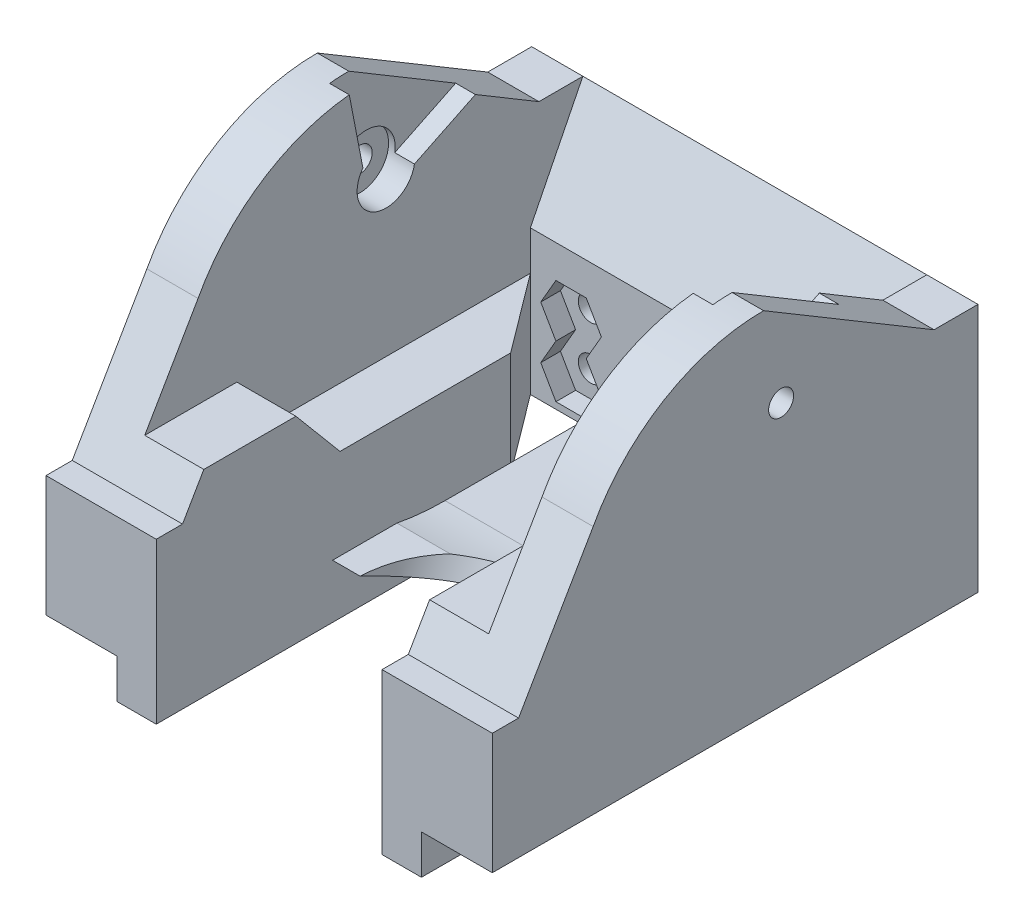
SolidWorks part; units mm, degrees
ref_plane "Alzado" through (0, 0, 0) normal (0, 0, 1) x (1, 0, 0)
ref_plane "Planta" through (0, 0, 0) normal (0, 1, 0) x (1, 0, 0)
ref_plane "Vista lateral" through (0, 0, 0) normal (1, 0, 0) x (0, 0, -1)
sketch "Croquis1" plane through (0, 0, 0) normal (0, 0, 1) x (1, 0, 0)
  line L1 (-48.8873, 14.6225) -> (-14.8873, 14.6225)
  line L2 (-48.8873, 14.6225) -> (-48.8873, -4.3775)
  line L3 (-48.8873, -4.3775) -> (-14.8873, -4.3775)
  line L4 (-14.8873, 14.6225) -> (-14.8873, -4.3775)
  dimension "D1" = 19
  dimension "D2" = 34
extrude "Saliente-Extruir1" add sketch "Croquis1" along normal blind 35
sketch "Croquis2" plane through (0, -4.3775, 0) normal (0, -1, 0) x (1, 0, 0)
  line L0 (-48.8873, 35) -> (-14.8873, 35) construction
  line L1 (-44.9873, 35) -> (-18.7873, 35)
  line L2 (-44.9873, 35) -> (-44.9873, 4)
  line L3 (-44.9873, 4) -> (-18.7873, 4)
  line L4 (-18.7873, 35) -> (-18.7873, 4)
  line L5 (-48.8873, 35) -> (-48.8873, 0) construction
  line L6 (-14.8873, 35) -> (-14.8873, 0) construction
  line L7 (-48.8873, 0) -> (-14.8873, 0) construction
  dimension "D1" = 3.9
  dimension "D2" = 3.9
  dimension "D3" = 26.2
  dimension "D4" = 4
extrude "Cortar-Extruir1" cut sketch "Croquis2" against normal blind 25
sketch "Croquis4" plane through (-18.7873, 0, 0) normal (-1, 0, 0) x (0, 0, 1)
  line L0 (4, 14.6225) -> (4, 6.6225)
  line L1 (4, 14.6225) -> (4, -4.3775) construction
  line L2 (4, 6.6225) -> (0, 14.6225)
  line L3 (0, 14.6225) -> (4, 14.6225)
extrude "Cortar-Extruir3" cut sketch "Croquis4" along normal up to vertex (26.2 mm away) up to point (-44.9873, 14.6225, 4)
sketch "Croquis9" plane through (-14.8873, 0, 0) normal (1, 0, 0) x (0, 0, -1)
  line L0 (-35, 14.6225) -> (0, 14.6225) construction
  line L1 (-29.3158, 14.6225) -> (-3.3495, 14.6225)
  line L7 (-35, -4.3775) -> (0, -4.3775) construction
  arc A0 (-29.3158, 14.6225) -> (-3.3495, 14.6225) centre (-16.3327, 7.6225) cw
  dimension "D2" = 12
extrude "Saliente-Extruir2" add sketch "Croquis9" against normal up to vertex (34 mm away) up to point (-48.8873, 14.6225, 35)
sketch "Croquis10" plane through (0, 14.6225, 0) normal (0, -1, 0) x (1, 0, 0)
  line L1 (-44.9873, 29.3158) -> (-18.7873, 29.3158)
  line L2 (-44.9873, 29.3158) -> (-44.9873, 3.3495)
  line L3 (-44.9873, 3.3495) -> (-18.7873, 3.3495)
  line L4 (-18.7873, 29.3158) -> (-18.7873, 3.3495)
extrude "Cortar-Extruir4" cut sketch "Croquis10" against normal blind 10
sketch "Croquis18" plane through (0, 0, 0) normal (0, 0, -1) x (-1, 0, 0)
  line L0 (48.8873, -4.3775) -> (14.8873, -4.3775) construction
  line L2 (48.8873, 14.6225) -> (48.8873, -4.3775) construction
  circle A0 centre (41.8873, -1.8775) radius 0.95
  circle A1 centre (21.8873, -1.8775) radius 0.95
  circle A2 centre (21.8873, 2.1225) radius 0.95
  circle A3 centre (41.8873, 2.1225) radius 0.95
  dimension "D1" = 2.5
  dimension "D2" = 7
  dimension "D5" = 4
  dimension "D3" = 2
  dimension "D4" = 2
extrude "Cortar-Extruir11" cut sketch "Croquis18" against normal up to vertex (4 mm away) up to point (-18.7873, -4.3775, 4)
sketch "Croquis19" plane through (0, 0, 4) normal (0, 0, 1) x (1, 0, 0)
  line L0 (-44.1973, -1.8775) -> (-43.0423, -3.878)
  line L1 (-24.1973, -1.8775) -> (-23.0423, -3.878)
  line L2 (-23.0423, -3.878) -> (-20.7323, -3.878)
  line L3 (-20.7323, -3.878) -> (-19.5773, -1.8775)
  line L4 (-19.5773, -1.8775) -> (-20.732, 0.1225)
  line L6 (-23.0426, 0.1225) -> (-24.1973, -1.8775)
  line L7 (-43.0423, -3.878) -> (-40.7323, -3.878)
  line L8 (-40.7323, -3.878) -> (-39.5773, -1.8775)
  line L9 (-39.5773, -1.8775) -> (-40.732, 0.1225)
  line L11 (-43.0426, 0.1225) -> (-44.1973, -1.8775)
  line L12 (-44.1973, 2.1225) -> (-43.0426, 0.1225)
  line L14 (-40.732, 0.1225) -> (-39.5773, 2.1225)
  line L15 (-39.5773, 2.1225) -> (-40.7323, 4.1231)
  line L16 (-40.7323, 4.1231) -> (-43.0423, 4.1231)
  line L17 (-43.0423, 4.1231) -> (-44.1973, 2.1225)
  line L18 (-24.1973, 2.1225) -> (-23.0426, 0.1225)
  line L20 (-20.732, 0.1225) -> (-19.5773, 2.1225)
  line L21 (-19.5773, 2.1225) -> (-20.7323, 4.1231)
  line L22 (-20.7323, 4.1231) -> (-23.0423, 4.1231)
  line L23 (-23.0423, 4.1231) -> (-24.1973, 2.1225)
  line L45 (-20.7323, 0.1231) -> (-23.0423, 0.1231) [skipped]
  line L46 (-23.0423, 0.122) -> (-20.7323, 0.122) [skipped]
  line L47 (-43.0423, 0.122) -> (-40.7323, 0.122) [skipped]
  circle A0 centre (-41.8873, -1.8775) radius 2.0005 construction
  circle A1 centre (-21.8873, -1.8775) radius 2.0005 construction
  circle A2 centre (-41.8873, 2.1225) radius 2.0005 construction
  circle A3 centre (-21.8873, 2.1225) radius 2.0005 construction
  dimension "D2" = 2
  dimension "D3" = 2
extrude "Cortar-Extruir12" cut sketch "Croquis19" against normal blind 1.5
sketch "Croquis21" plane through (-14.8873, 0, 0) normal (1, 0, 0) x (0, 0, -1)
  line L0 (0, -4.3775) -> (0, 14.6225) construction
  line L2 (-35, -4.3775) -> (0, -4.3775) construction
  circle A0 centre (-15, 15.6225) radius 0.95
  dimension "D1" = 15
  dimension "D2" = 20
extrude "Cortar-Extruir14" cut sketch "Croquis21" against normal up to vertex (34 mm away) up to point (-48.8873, 14.6225, 3.3495)
sketch "Croquis23" plane through (0, -4.3775, 0) normal (0, -1, 0) x (1, 0, 0)
  line L0 (-44.9873, 35) -> (-40.4873, 35)
  line L1 (-40.4873, 35) -> (-40.4873, 10)
  line L2 (-40.4873, 10) -> (-44.9873, 4)
  line L3 (-44.9873, 35) -> (-44.9873, 4) construction
  line L4 (-44.9873, 4) -> (-44.9873, 35)
  line L5 (-18.7873, 35) -> (-23.2873, 35)
  line L6 (-23.2873, 35) -> (-23.2873, 10)
  line L7 (-23.2873, 10) -> (-18.7873, 4)
  line L8 (-18.7873, 4) -> (-18.7873, 35)
  dimension "D1" = 25
  dimension "D2" = 25
extrude "Saliente-Extruir3" add sketch "Croquis23" against normal blind 8
sketch "Croquis25" plane through (0, -4.3775, 0) normal (0, -1, 0) x (1, 0, 0)
  line L0 (-40.4873, 35) -> (-43.4873, 35)
  line L1 (-20.2873, 35) -> (-23.2873, 35)
  line L2 (-43.4873, 35) -> (-43.4873, 10)
  line L3 (-43.4873, 10) -> (-40.4873, 10)
  line L4 (-40.4873, 35) -> (-40.4873, 10)
  line L10 (-20.2873, 35) -> (-20.2873, 10)
  line L11 (-20.2873, 10) -> (-23.2873, 10)
  line L12 (-23.2873, 35) -> (-23.2873, 10)
  dimension "D1" = 3
  dimension "D2" = 3
extrude "Saliente-Extruir4" add sketch "Croquis25" along normal blind 3
sketch "Croquis43" plane through (0, 3.6225, 0) normal (0, 1, 0) x (1, 0, 0)
  line L0 (-23.2873, -35) -> (-23.2873, -10) construction
  line L1 (-18.7873, -35) -> (-23.2873, -35)
  line L2 (-18.7873, -35) -> (-18.7873, -23)
  line L3 (-18.7873, -23) -> (-23.2873, -23)
  line L4 (-23.2873, -35) -> (-23.2873, -23)
  line L5 (-44.9873, -35) -> (-44.9873, -4) construction
  line L6 (-40.4873, -35) -> (-44.9873, -35)
  line L7 (-40.4873, -35) -> (-40.4873, -23)
  line L8 (-40.4873, -23) -> (-44.9873, -23)
  line L9 (-44.9873, -35) -> (-44.9873, -23)
  dimension "D1" = 12
  dimension "D2" = 12
extrude "Saliente-Extruir8" add sketch "Croquis43" along normal blind 4
sketch "Croquis27" plane through (-14.8873, 0, 0) normal (1, 0, 0) x (0, 0, -1)
  line L0 (-13.5494, -0.9426) -> (-12.6355, -5.8873)
  line L1 (-33.492, 4.3837) -> (-29.3712, 7.2574)
  arc A2 (-29.3712, 7.2574) -> (-13.5494, -0.9426) centre (-15, 15.6225) ccw
  arc A3 (-33.492, 4.3837) -> (-12.6355, -5.8873) centre (-15, 15.6225) ccw
  dimension "D2" = 21.6395
sketch "Croquis29" plane through (-18.7873, 0, 0) normal (-1, 0, 0) x (0, 0, 1)
  line L0 (17.7974, 22.2996) -> (16.5, 15.6225)
  line L1 (6.2969, 18.4321) -> (13.7431, 14.804)
  arc A0 (6.2969, 18.4321) -> (17.7974, 22.2996) centre (16.3327, 7.6225) cw
  arc A1 (29.3158, 14.6225) -> (3.3495, 14.6225) centre (16.3327, 7.6225) ccw construction
  arc A2 (16.5, 15.6225) -> (13.7431, 14.804) centre (15, 15.6225) cw
extrude "Cortar-Extruir20" cut sketch "Croquis29" against normal blind 1.5
extrude "Cortar-Extruir21" cut sketch "Croquis29<2>" along normal blind 27.7
sketch "Croquis29<2>" plane through (-18.7873, 0, 0) normal (-1, 0, 0) x (0, 0, 1) same geometry as "Croquis29"
sketch "Croquis30" plane through (-48.8873, 0, 0) normal (-1, 0, 0) x (0, 0, 1)
  line L0 (29.3158, 14.6225) -> (35, 4.8278)
  line L1 (35, 14.6225) -> (35, -4.3775) construction
  line L2 (35, 4.8278) -> (35, 14.6225)
  line L3 (35, 14.6225) -> (29.3158, 14.6225)
extrude "Cortar-Extruir22" cut sketch "Croquis30" against normal up to vertex (34 mm away) up to point (-14.8873, 14.6225, 35)
sketch "Croquis35" plane through (0, -4.3775, 0) normal (0, -1, 0) x (1, 0, 0)
  line L0 (-20.2873, 23.2623) -> (-14.8873, 23.2623)
  line L2 (-20.2873, 23.2623) -> (-14.8873, 23.2623) construction
  line L4 (-14.8873, 23.2623) -> (-14.8873, 27.7963)
  line L5 (-14.8873, 35) -> (-14.8873, 0) construction
  line L6 (-14.8873, 27.7963) -> (-20.2873, 23.2623)
sketch "Croquis36" plane through (-18.7873, 0, 0) normal (-1, 0, 0) x (0, 0, 1)
  circle A0 centre (15, 15.6225) radius 2.2
extrude "Cortar-Extruir24" cut sketch "Croquis36" against normal blind 2
extrude "Cortar-Extruir25" cut sketch "Croquis36<2>" along normal blind 28.2
sketch "Croquis36<2>" plane through (-18.7873, 0, 0) normal (-1, 0, 0) x (0, 0, 1) same geometry as "Croquis36"
sketch "Croquis38" plane through (-48.8873, 0, 0) normal (-1, 0, 0) x (0, 0, 1)
  line L0 (3.3495, 14.6225) -> (16.3327, 22.3725)
  line L1 (16.3327, 22.3725) -> (3.3495, 22.3725)
  line L2 (3.3495, 22.3725) -> (3.3495, 14.6225)
  arc A0 (29.3158, 14.6225) -> (3.3495, 14.6225) centre (16.3327, 7.6225) ccw construction
extrude "Cortar-Extruir26" cut sketch "Croquis38" against normal up to vertex (34 mm away) up to point (-14.8873, 14.6225, 3.3495)
sketch "Croquis40" plane through (-48.8873, 0, 0) normal (-1, 0, 0) x (0, 0, 1)
  line L0 (24.4625, 4.9679) -> (27.805, 0.9845)
  line L1 (27.805, 0.9845) -> (27.1921, 0.4702)
  line L2 (27.1921, 0.4702) -> (23.8496, 4.4537)
  line L3 (23.5, 4.1807) -> (26.4826, -0.0789)
  line L4 (26.4826, -0.0789) -> (25.8272, -0.5377)
  line L5 (25.8272, -0.5377) -> (22.8446, 3.7219)
  line L6 (22.4696, 3.4848) -> (25.0696, -1.0186)
  line L7 (24.4625, 4.9679) -> (23.8496, 4.4537)
  line L8 (25.0696, -1.0186) -> (24.3768, -1.4186)
  line L9 (24.3768, -1.4186) -> (21.7768, 3.0848)
  line L10 (22.8446, 3.7219) -> (23.5, 4.1807)
  line L11 (21.3819, 2.8831) -> (23.5795, -1.8297)
  line L12 (23.5795, -1.8297) -> (22.8544, -2.1678)
  line L13 (22.4696, 3.4848) -> (21.7768, 3.0848)
  line L14 (22.8544, -2.1678) -> (20.6568, 2.545)
  line L16 (21.3819, 2.8831) -> (20.6568, 2.545)
  circle A1 centre (15, 15.6225) radius 0.95 construction
  dimension "D2" = 14.2443
  dimension "D3" = 14.248
  dimension "D4" = 14.2464
  dimension "D5" = 0.8
  dimension "D6" = 14.2429
  dimension "D8" = 0.8
  dimension "D9" = 0.8
  dimension "D11" = 0.8
sketch "Croquis41" plane through (-20.2873, 0, 0) normal (1, 0, 0) x (0, 0, -1)
  line L0 (-10, -4.3775) -> (-10, -7.3775)
  line L1 (-10, -7.3775) -> (-10, -4.3775) construction
  line L2 (-10, -7.3775) -> (-13, -7.3775)
  line L3 (-10, -7.3775) -> (-35, -7.3775) construction
  line L4 (-13, -7.3775) -> (-10, -4.3775)
extrude "Cortar-Extruir28" cut sketch "Croquis41" against normal up to vertex (23.2 mm away) up to point (-43.4873, -7.3775, 10)
sketch "Croquis44" plane through (-18.7873, 0, 0) normal (-1, 0, 0) x (0, 0, 1)
  line L0 (23, 7.6225) -> (26.3626, 7.6225)
  line L1 (33.3781, 7.6225) -> (23, 7.6225) construction
  line L2 (26.3626, 7.6225) -> (23, 3.6225)
  line L3 (23, 3.6225) -> (23, 7.6225)
extrude "Cortar-Extruir29" cut sketch "Croquis44" along normal up to vertex (26.2 mm away) up to point (-44.9873, 7.6225, 23)
sketch "Croquis24" plane through (-14.8873, 0, 0) normal (1, 0, 0) x (0, 0, -1)
  line L0 (-15, -3.6275) -> (-15, -5.1273)
  line L1 (-31.1427, 5.1356) -> (-32.3723, 4.2754)
  arc A2 (-31.1427, 5.1356) -> (-15, -3.6275) centre (-15, 15.6225) ccw
  arc A3 (-32.3723, 4.2754) -> (-15, -5.1273) centre (-15, 15.6225) ccw
  dimension "D1" = 19.25
  dimension "D2" = 20.7498
sketch "Croquis45" plane through (-23.2873, 0, 0) normal (-1, 0, 0) x (0, 0, 1)
  line L0 (32.3723, 4.2754) -> (31.1427, 5.1356)
  line L1 (15, -3.6275) -> (15, -5.1273)
  line L2 (15, -3.6275) -> (15, -5.1273) construction
  arc A0 (15, -3.6275) -> (31.1427, 5.1356) centre (15, 15.6225) ccw construction
  arc A1 (32.3723, 4.2754) -> (15, -5.1273) centre (15, 15.6225) cw
  arc A2 (15, -3.6275) -> (31.1427, 5.1356) centre (15, 15.6225) ccw
extrude "Saliente-Extruir9" add sketch "Croquis45" along normal up to vertex (17.2 mm away) separate body up to point (-40.4873, -7.3775, 13)
ref_plane "Plano1" through (-31.8873, 4.2754, 32.3723) normal (1, 0, 0) x (0, 0, -1)
sketch "Croquis47" plane through (-31.8873, 4.2754, 32.3723) normal (1, 0, 0) x (0, 0, -1)
  line L0 (17.3723, 11.3471) -> (17.3723, -21.3789) construction
  line L1 (17.3723, 11.3471) -> (0.4676, -24.9052) construction
  line L2 (17.3723, 11.3471) -> (-2.6277, -23.2939) construction
  line L3 (17.3723, 11.3471) -> (-5.5707, -21.419) construction
  line L4 (17.3723, 11.3471) -> (-5.5707, -21.419)
  line L5 (17.3723, 11.3471) -> (-2.6277, -23.2939)
  line L6 (17.3723, 11.3471) -> (0.4676, -24.9052)
  dimension "D1" = 25
  dimension "D2" = 30
  dimension "D3" = 35
ref_plane "Plano2" through (-31.8873, -17.1435, 37.9431) normal (0, -0.8192, 0.5736) x (-1, 0, 0)
sketch "Croquis48" plane through (-31.8873, -17.1435, 37.9431) normal (0, -0.8192, 0.5736) x (-1, 0, 0)
  line L3 (6.5, 0) -> (6.5, -15)
  line L4 (6.5, -15) -> (-6.5, -15)
  line L5 (-6.5, -15) -> (-6.5, 0)
  arc A2 (6.5, 0) -> (-6.5, 0) centre (0, 0) ccw
ref_plane "Plano3" through (-31.8873, -19.0185, 35) normal (0, -0.866, 0.5) x (-1, 0, 0)
ref_plane "Plano4" through (-31.8873, -20.6298, 31.9047) normal (0, -0.9063, 0.4226) x (-1, 0, 0)
sketch "Croquis49" plane through (-31.8873, -19.0185, 35) normal (0, -0.866, 0.5) x (-1, 0, 0)
  circle A0 centre (0, 0) radius 6.5
sketch "Croquis50" plane through (-31.8873, -20.6298, 31.9047) normal (0, -0.9063, 0.4226) x (-1, 0, 0)
  circle A0 centre (0, 0) radius 6.5
sweep "Cortar-Barrer2" cut profiles "Croquis48" path "Croquis47"
sketch "Croquis51" plane through (-31.8873, 4.2754, 32.3723) normal (1, 0, 0) x (0, 0, -1)
  line L0 (17.3723, 11.3471) -> (-2.6277, -23.2939)
sweep "Cortar-Barrer3" cut profiles "Croquis49" path "Croquis51"
sketch "Croquis52" plane through (-31.8873, 4.2754, 32.3723) normal (1, 0, 0) x (0, 0, -1)
  line L0 (17.3723, 11.3471) -> (0.4676, -24.9052)
sweep "Cortar-Barrer4" cut profiles "Croquis50" path "Croquis52"
sketch "Croquis53" plane through (0, 0, 15) normal (0, 0, -1) x (-1, 0, 0)
  line L1 (40.4873, -5.1273) -> (23.2873, -5.1273)
  line L2 (40.4873, -5.1273) -> (40.4873, -3.6275)
  line L3 (40.4873, -3.6275) -> (23.2873, -3.6275)
  line L4 (23.2873, -5.1273) -> (23.2873, -3.6275)
extrude "Saliente-Extruir13" add sketch "Croquis53" along normal up to vertex (11 mm away) separate body up to point (-18.7873, -4.3775, 4)
sketch "Croquis55" plane through (-40.4873, 0, 0) normal (-1, 0, 0) x (0, 0, 1)
  line L0 (4, -5.1273) -> (4, -4.3774)
  line L1 (4, -5.1273) -> (4, -3.6275) construction
  line L2 (4, -4.3774) -> (0, -4.3774)
  line L3 (0, -4.3774) -> (4, -5.1273)
extrude "Saliente-Extruir14" add sketch "Croquis55" against normal up to vertex (17.2 mm away) up to point (-23.2873, -5.1273, 4)
sketch "Croquis56" plane through (0, 0, 35) normal (0, 0, 1) x (1, 0, 0)
  line L0 (-23.2873, -7.3775) -> (-20.2873, -7.3775)
  line L1 (-20.2873, -7.3775) -> (-20.2873, -4.3775)
  line L2 (-20.2873, -4.3775) -> (-14.8873, -4.3775)
  line L3 (-14.8873, -4.3775) -> (-14.8873, 4.8278)
  line L4 (-14.8873, 4.8278) -> (-23.2873, 4.8278)
  line L5 (-23.2873, 4.8278) -> (-23.2873, -7.3775)
  line L6 (-40.4873, -7.3775) -> (-40.4873, 4.8278)
  line L7 (-40.4873, 4.8278) -> (-48.8873, 4.8278)
  line L8 (-48.8873, 4.8278) -> (-48.8873, -4.3775)
  line L9 (-48.8873, -4.3775) -> (-43.4873, -4.3775)
  line L10 (-43.4873, -4.3775) -> (-43.4873, -7.3775)
  line L11 (-43.4873, -7.3775) -> (-40.4873, -7.3775)
extrude "Saliente-Extruir15" add sketch "Croquis56" along normal blind 2
sketch "Croquis58" plane through (0, 0, 37) normal (0, 0, 1) x (1, 0, 0)
  line L0 (-40.4873, -7.3775) -> (-40.4873, 4.8278) construction
  line L2 (-40.4873, -1.2748) -> (-40.4873, 6.807)
  line L3 (-40.4873, 6.807) -> (-23.2873, 6.807)
  line L4 (-23.2873, -1.2748) -> (-23.2873, 6.807)
  line L5 (-23.2873, -1.2748) -> (-23.2873, -3.2748)
  line L6 (-23.2873, 4.8278) -> (-23.2873, -7.3775) construction
  line L7 (-23.2873, -3.2748) -> (-40.4873, -3.2748)
  line L8 (-40.4873, -3.2748) -> (-40.4873, -1.2748)
extrude "Cortar-Extruir30" cut sketch "Croquis58" against normal blind 20
